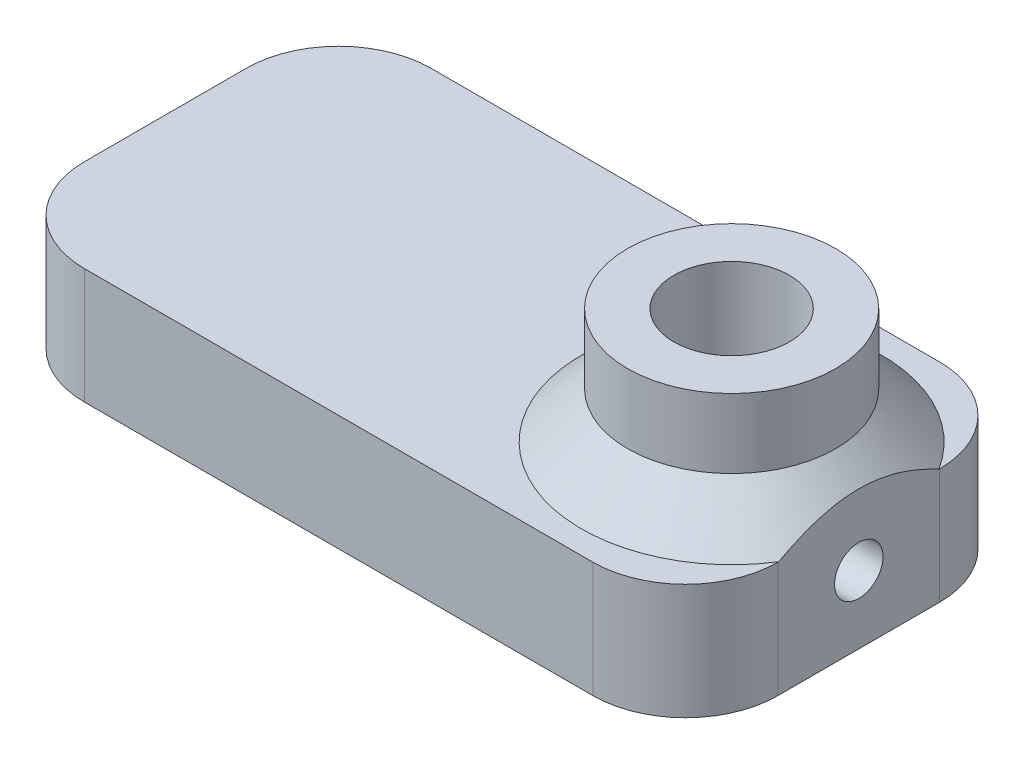
SolidWorks part; units mm, degrees
ref_plane "Front Plane" through (0, 0, 0) normal (0, 0, 1) x (1, 0, 0)
ref_plane "Top Plane" through (0, 0, 0) normal (0, 1, 0) x (1, 0, 0)
ref_plane "Right Plane" through (0, 0, 0) normal (1, 0, 0) x (0, 0, -1)
sketch "Sketch1" plane through (0, 0, 0) normal (0, 1, 0) x (1, 0, 0)
  line L1 (-49, 15) -> (11, 15)
  line L2 (-49, 15) -> (-49, -15)
  line L3 (-49, -15) -> (11, -15)
  line L4 (11, 15) -> (11, -15)
  circle A0 centre (0, 0) radius 5
  circle A1 centre (0, 0) radius 9
  point P8 (11, 0)
  dimension "D1" = 10
  dimension "D2" = 18
  dimension "D3" = 30
  dimension "D4" = 60
  dimension "D5" = 2
extrude "Base" add sketch "Sketch1" along normal blind 10 contours L4 A1 L1 L2 L3 | A1 A0 region at (-22.1283, 0, 0) region at (-8.7454, 0, 0)
fillet "AddALittleBeauty" radius 8 4 edges at (-49, 5, 15) (-49, 5, -15) (11, 5, -15) (11, 5, 15)
extrude "RodHolder" add sketch "Sketch1<3>" along normal blind 20 contours A1 A0 region at (-8.7454, 0, 0)
sketch "Sketch1<3>" plane through (0, 0, 0) normal (0, 1, 0) x (1, 0, 0) same geometry as "Sketch1"
hole_wizard "M5x0.8 Tapped Hole for fixing rod" positions "Sketch3" profile "Sketch4" tap size "M5x0.8" standard "ANSI Metric"
sketch "Sketch3" plane through (11, 0, 0) normal (1, 0, 0) x (0, 0, -1)
  point P0 (0, 5.8799)
cosmetic thread "Hole Thread1" parameters "D1"=4.4624, "D2"=5
sketch "Sketch4" plane through (11, 5.8799, 0) normal (0, 1, 0) x (0, 0, -1)
  line L0 (0, 0) -> (0, 9.6618)
  line L1 (0, 9.6618) -> (2.1, 8.4)
  line L2 (2.1, 8.4) -> (2.1, 0)
  line L5 (2.1, 0) -> (0, 0)
  line L10 (0, 9.6618) -> (-2.1, 8.4) construction
  line L11 (0, -6.35) -> (0, 107.95) construction
  dimension "Tap Drill Dia." = 4.2
  dimension "Tap Drill Depth" = 8.4
  dimension "Drill Angle" = 118
chamfer "Chamfer1" distance 4 angle 45 1 edges at (0, 10, 9)
equation "\"D2@Sketch1\"=10.00mm+8"
